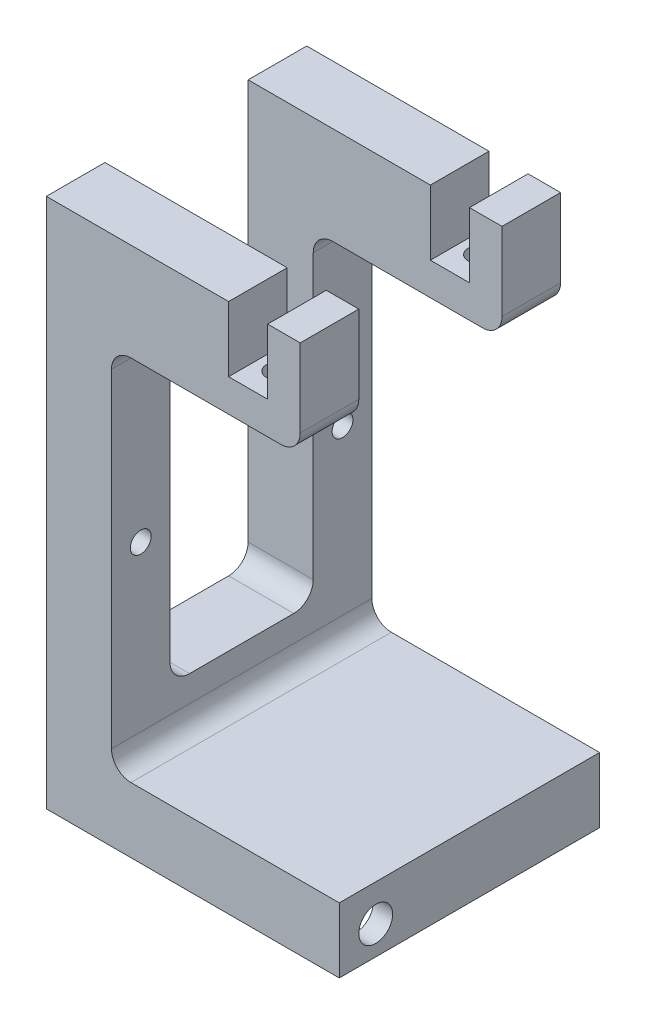
SolidWorks part; units mm, degrees
ref_plane "Front Plane" through (0, 0, 0) normal (0, 0, 1) x (1, 0, 0)
ref_plane "Top Plane" through (0, 0, 0) normal (0, 1, 0) x (1, 0, 0)
ref_plane "Right Plane" through (0, 0, 0) normal (1, 0, 0) x (0, 0, -1)
sketch "Sketch1" plane through (0, 0, 0) normal (0, 0, 1) x (1, 0, 0)
  line L0 (10, 10) -> (45, 10)
  line L1 (0, 0) -> (45, 0)
  line L2 (0, 0) -> (0, 81.5)
  line L3 (0, 81.5) -> (28, 81.5)
  line L5 (10, 10) -> (10, 66.5)
  line L6 (10, 66.5) -> (39, 66.5)
  line L8 (45, 10) -> (45, 0)
  line L19 (39, 81.5) -> (39, 66.5)
  line L20 (28, 81.5) -> (34, 81.5) construction
  line L21 (28, 81.5) -> (34, 81.5) construction
  line L22 (28, 81.5) -> (28, 71.5)
  line L23 (28, 71.5) -> (34, 71.5)
  line L24 (34, 81.5) -> (34, 71.5)
  line L25 (34, 81.5) -> (39, 81.5)
  dimension "D2" = 81.5
  dimension "D3" = 39
  dimension "D4" = 45
  dimension "D5" = 5
  dimension "D6" = 6
  dimension "D7" = 10
  dimension "D1" = 10
  dimension "D8" = 15
  dimension "D9" = 10
extrude "Boss-Extrude1" add sketch "Sketch1" along normal blind 40
sketch "Sketch2" plane through (0, 0, 0) normal (-1, 0, 0) x (0, 0, 1)
  line L0 (40, 81.5) -> (0, 81.5) construction
  line L1 (9, 81.5) -> (31, 81.5)
  line L2 (9, 81.5) -> (9, 17)
  line L3 (9, 17) -> (31, 17)
  line L4 (31, 81.5) -> (31, 17)
  line L5 (40, 0) -> (0, 0) construction
  point P9 (20, 0)
  point P10 (20, 17)
  dimension "D1" = 17
  dimension "D2" = 22
extrude "Cut-Extrude1" cut sketch "Sketch2" against normal through all
sketch "Sketch4" plane through (0, 71.5, 0) normal (0, 1, 0) x (1, 0, 0)
  line L0 (31, -31) -> (31, -40) construction
  line L1 (34, -31) -> (28, -31) construction
  line L2 (34, -40) -> (28, -40) construction
  line L3 (0, -20) -> (45, -20) construction
  line L4 (0, -9) -> (0, -31) construction
  line L5 (45, -40) -> (45, 0) construction
  circle A0 centre (31, -35.5) radius 1.7
  circle A1 centre (31, -4.5) radius 1.7
  dimension "D1" = 3.4
extrude "Cut-Extrude2" cut sketch "Sketch4" against normal up to next
sketch "Sketch7" plane through (45, 0, 0) normal (1, 0, 0) x (0, 0, -1)
  line L1 (-40, 0) -> (-40, 10) construction
  line L2 (-40, 10) -> (0, 10) construction
  circle A0 centre (-34.4, 4.4) radius 2.6
  dimension "D1" = 5.2
  dimension "D2" = 5.6
  dimension "D3" = 5.6
extrude "Cut-Extrude3" cut sketch "Sketch7" against normal blind 10
fillet "Fillet1" radius 3 3 edges at (10, 10, 20) (5, 17, 31) (5, 17, 9)
fillet "Fillet2" radius 3 4 edges at (39, 66.5, 4.5) (39, 66.5, 35.5) (10, 66.5, 35.5) (10, 66.5, 4.5)
sketch "Sketch8" plane through (0, 0, 0) normal (0, -1, 0) x (1, 0, 0)
  line L8 (3, 3) -> (42, 3)
  line L9 (42, 3) -> (42, 37)
  line L10 (42, 37) -> (3, 37)
  line L11 (3, 37) -> (3, 3)
  line L12 (3, 3) -> (42, 3)
  line L13 (42, 3) -> (42, 37)
  line L14 (42, 37) -> (3, 37)
  line L15 (3, 37) -> (3, 3)
  dimension "D1" = 3
extrude "Cut-Extrude4" cut sketch "Sketch8" against normal blind 7
sketch "Sketch9" plane through (10, 0, 0) normal (1, 0, 0) x (0, 0, -1)
  line L0 (-4.5, 63.5) -> (-4.5, 13) construction
  line L1 (0, 63.5) -> (-9, 63.5) construction
  line L2 (-40, 13) -> (0, 13) construction
  line L3 (-20, 17) -> (-20, 82.5748) construction
  line L4 (-12, 17) -> (-28, 17) construction
  circle A0 centre (-4.5, 38.25) radius 1.6
  circle A1 centre (-35.5, 38.25) radius 1.6
  dimension "D1" = 3.2
extrude "Cut-Extrude5" cut sketch "Sketch9" against normal up to next
